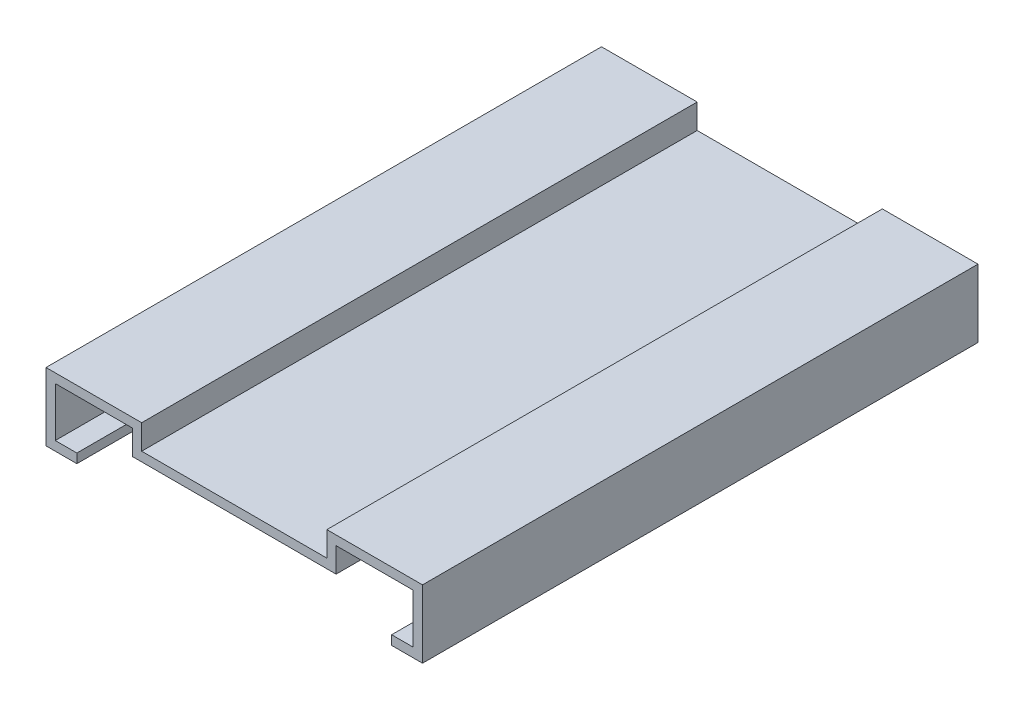
SolidWorks part; units mm, degrees
ref_plane "Front Plane" through (0, 0, 0) normal (0, 0, 1) x (1, 0, 0)
ref_plane "Top Plane" through (0, 0, 0) normal (0, 1, 0) x (1, 0, 0)
ref_plane "Right Plane" through (0, 0, 0) normal (1, 0, 0) x (0, 0, -1)
sketch "Sketch1" plane through (0, 0, 0) normal (0, 0, 1) x (1, 0, 0)
  line L1 (61, -11) -> (-61, -11)
  line L2 (61, -11) -> (61, 11)
  line L3 (61, 11) -> (-61, 11)
  line L4 (-61, -11) -> (-61, 11)
  line L5 (61, -11) -> (-61, 11) construction
  line L6 (61, 11) -> (-61, -11) construction
  point P0 (0, 0)
  dimension "D1" = 122
  dimension "D2" = 22
extrude "Boss-Extrude1" add sketch "Sketch1" along normal blind 90 and the other way blind 90
sketch "Sketch2" plane through (0, 0, 90) normal (0, 0, 1) x (1, 0, 0)
  line L0 (61, 11) -> (-61, 11) construction
  line L1 (33, -8) -> (58, -8)
  line L2 (33, -8) -> (33, 8)
  line L3 (33, 8) -> (58, 8)
  line L4 (58, -8) -> (58, 8)
  line L5 (33, -8) -> (58, 8) construction
  line L6 (33, 8) -> (58, -8) construction
  line L7 (-61, -11) -> (61, -11) construction
  line L8 (61, -11) -> (61, 11) construction
  point P0 (45.5, 0)
  dimension "D1" = 3
  dimension "D2" = 3
  dimension "D3" = 3
  dimension "D4" = 25
extrude "Cut-Extrude1" cut sketch "Sketch2" against normal through all both and the other way through all
mirror "Mirror1" about plane through (0, 0, 0) normal (1, 0, 0) of "Cut-Extrude1"
sketch "Sketch3" plane through (0, 0, 90) normal (0, 0, 1) x (1, 0, 0)
  line L0 (61, 11) -> (-61, 11) construction
  line L1 (-30, 19) -> (30, 19)
  line L2 (-30, 19) -> (-30, 3)
  line L3 (-30, 3) -> (30, 3)
  line L4 (30, 19) -> (30, 3)
  line L5 (-30, 19) -> (30, 3) construction
  line L6 (-30, 3) -> (30, 19) construction
  point P0 (0, 11)
  dimension "D1" = 60
  dimension "D2" = 16
extrude "Cut-Extrude2" cut sketch "Sketch3" against normal through all
sketch "Sketch4" plane through (0, 0, 90) normal (0, 0, 1) x (1, 0, 0)
  line L0 (-61, -11) -> (61, -11) construction
  line L1 (30.0773, -22) -> (-30.0773, -22)
  line L2 (30.0773, -22) -> (30.0773, 0)
  line L3 (30.0773, 0) -> (-30.0773, 0)
  line L4 (-30.0773, -22) -> (-30.0773, 0)
  line L5 (30.0773, -22) -> (-30.0773, 0) construction
  line L6 (30.0773, 0) -> (-30.0773, -22) construction
  line L7 (-30, 3) -> (30, 3) construction
  point P0 (0, -11)
  dimension "D1" = 3
extrude "Cut-Extrude3" cut sketch "Sketch4" against normal through all
sketch "Sketch5" plane through (0, 0, 90) normal (0, 0, 1) x (1, 0, 0)
  line L0 (61, -11) -> (61, 11) construction
  line L1 (30.0773, -11) -> (51, -11)
  line L2 (30.0773, -11) -> (30.0773, 0)
  line L3 (30.0773, 0) -> (51, 0)
  line L4 (51, -11) -> (51, 0)
  dimension "D1" = 10
extrude "Cut-Extrude4" cut sketch "Sketch5" against normal through all
mirror "Mirror2" about plane through (0, 0, 0) normal (1, 0, 0) of "Cut-Extrude4"
